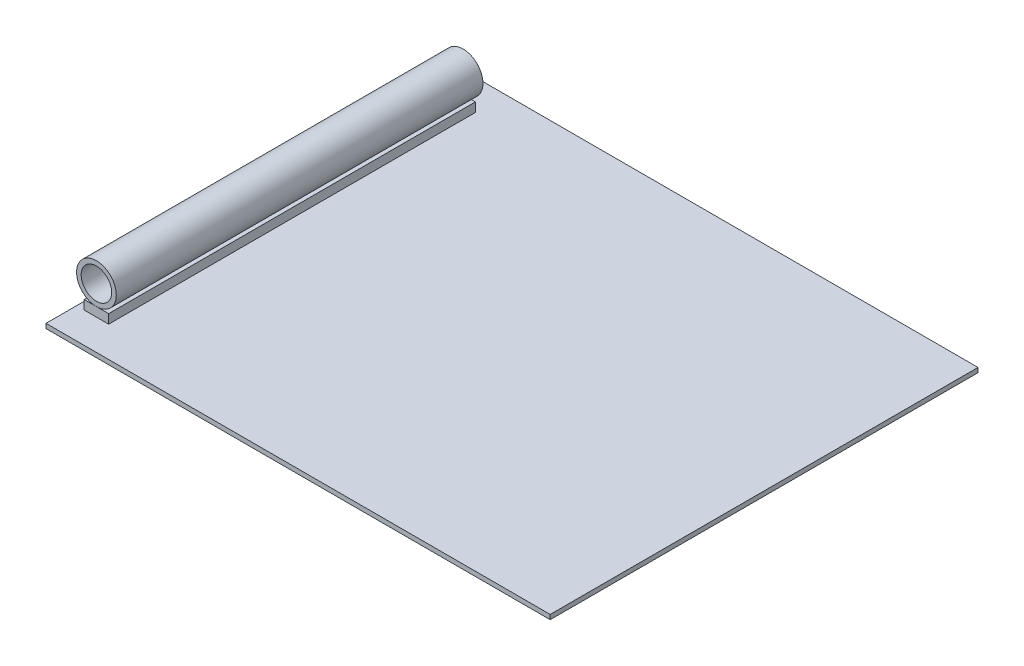
SolidWorks part; units mm, degrees
ref_plane "Plan de face" through (0, 0, 0) normal (0, 0, 1) x (1, 0, 0)
ref_plane "Plan de dessus" through (0, 0, 0) normal (0, 1, 0) x (1, 0, 0)
ref_plane "Plan de droite" through (0, 0, 0) normal (1, 0, 0) x (0, 0, -1)
sketch "Esquisse1" plane through (0, 0, 0) normal (0, 0, 1) x (1, 0, 0)
  line L1 (0, 0) -> (165, 0)
  line L2 (0, 0) -> (0, 1.5)
  line L3 (0, 1.5) -> (165, 1.5)
  line L4 (165, 0) -> (165, 1.5)
  line L5 (2.5, 1.5) -> (10.5, 1.5)
  line L6 (2.5, 1.5) -> (2.5, 4.5)
  line L7 (2.5, 4.5) -> (10.5, 4.5)
  line L8 (10.5, 1.5) -> (10.5, 4.5)
  circle A0 centre (6.5, 11) radius 5
  circle A1 centre (6.5, 11) radius 6.5
  point P13 (6.5, 4.5)
  dimension "D3" = 10
  dimension "D1" = 165
  dimension "D2" = 1.5
  dimension "D5" = 9.5
  dimension "D6" = 8
  dimension "D7" = 3
  dimension "D8" = 6.5
  dimension "D9" = 0
  dimension "D4" = 1.5
extrude "Boss.-Extru.1" add sketch "Esquisse1" along normal blind 70 and the other way blind 70 contours L3 L8 L7 L6 | A1 A0 | L3 L4 L1 L2 region at (2.0338, 15.4662, 0) region at (6.5, 3, 0)
sketch "Esquisse2" plane through (2.5, 0, 0) normal (-1, 0, 0) x (0, 0, 1)
  line L0 (0, 0) -> (0, 39.5353) construction
  line L1 (-70, 1.5) -> (-60, 1.5)
  line L2 (-70, 1.5) -> (-70, 18.5)
  line L3 (-70, 18.5) -> (-60, 18.5)
  line L4 (-60, 1.5) -> (-60, 18.5)
  line L5 (70, 1.5) -> (60, 1.5)
  line L6 (60, 1.5) -> (60, 18.5)
  line L7 (70, 1.5) -> (70, 18.5)
  line L8 (70, 18.5) -> (60, 18.5)
  dimension "D1" = 17
  dimension "D2" = 10
extrude "Enlèv. mat.-Extru.1" cut sketch "Esquisse2" against normal blind 20 and the other way blind 10
